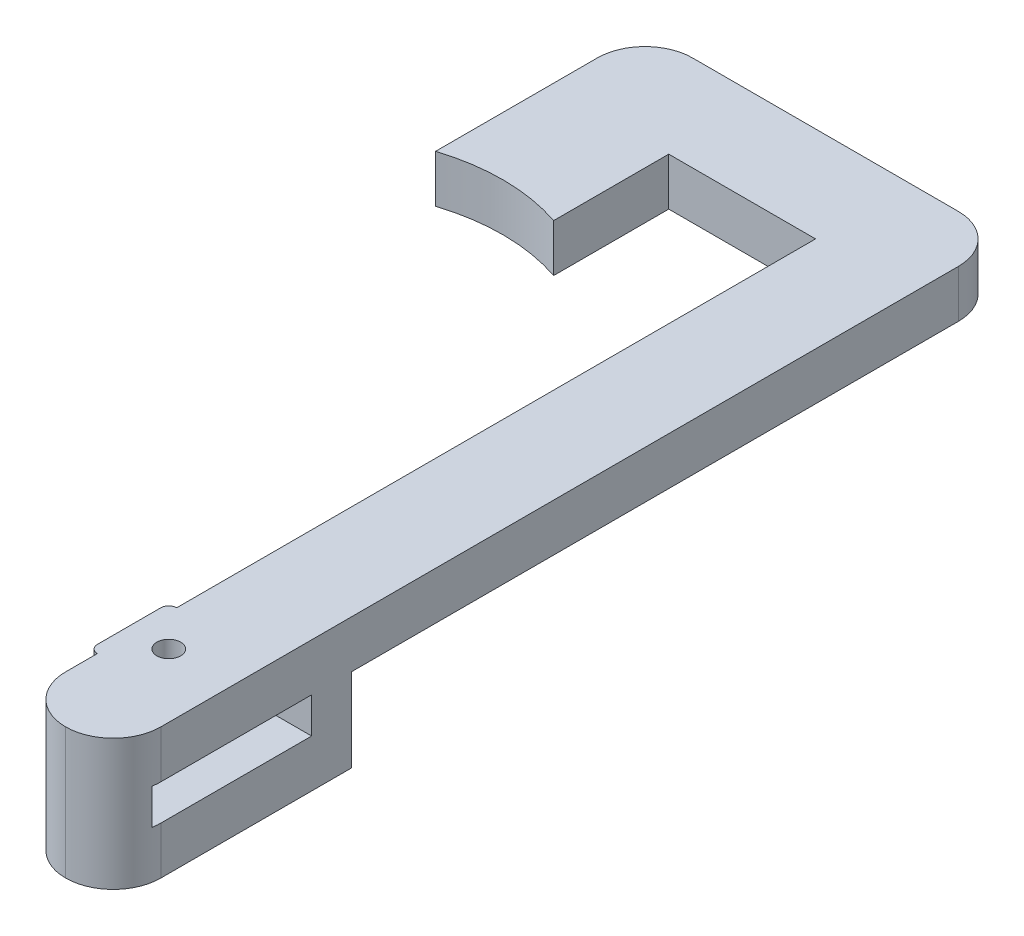
SolidWorks part; units mm, degrees
ref_plane "Front Plane" through (0, 0, 0) normal (0, 0, 1) x (1, 0, 0)
ref_plane "Top Plane" through (0, 0, 0) normal (0, 1, 0) x (1, 0, 0)
ref_plane "Right Plane" through (0, 0, 0) normal (1, 0, 0) x (0, 0, -1)
sketch "Sketch1" plane through (0, 0, 0) normal (0, 1, 0) x (1, 0, 0)
  line L0 (0, 0) -> (0, -7.5)
  line L15 (-2, -7.5) -> (4, -7.5)
  line L16 (-2, -7.5) -> (-2, 42.75)
  line L18 (4, -7.5) -> (4, 48.75)
  line L19 (-2, -2.9) -> (-2, -7.5)
  line L22 (0, 0) -> (-2, 0)
  line L23 (-11.25, 42.75) -> (-2, 42.75)
  line L26 (4, 48.75) -> (-18.75, 48.75)
  line L29 (-18.75, 48.75) -> (-18.75, 35.75)
  line L30 (-18.75, 35.75) -> (-11.25, 35.75)
  line L31 (-11.25, 42.75) -> (-11.25, 35.75)
  line L32 (0, 0) -> (4, 0)
  line L33 (-2, 42.75) -> (4, 42.75)
  line L34 (-18.75, 35.75) -> (-11.25, 35.75)
  line L35 (-18.75, 35.75) -> (-18.75, 28.3693)
  line L36 (-18.75, 28.3693) -> (-11.25, 28.3693)
  line L37 (-11.25, 35.75) -> (-11.25, 28.3693)
  line L38 (-2, 42.75) -> (-2, 48.75)
  line L39 (-11.25, 42.75) -> (-18.75, 42.75)
  line L40 (-11.25, 42.75) -> (-11.25, 48.75)
  line L42 (-2.5, 2.5) -> (-2, 2.5)
  line L43 (-2.5, 2.5) -> (-2.5, -2.5)
  line L44 (-2.5, -2.5) -> (-2, -2.5)
  line L45 (-2, 2.5) -> (-2, -2.5)
  line L46 (-2.5, 2.5) -> (-2, -2.5) construction
  line L47 (-2.5, -2.5) -> (-2, 2.5) construction
  point P0 (1, -7.5)
  point P4 (-2.25, 0)
  point P27 (0, 0)
  point P28 (0, 0)
  dimension "D1" = 9.25
  dimension "D2" = 2
  dimension "D3" = 4
  dimension "D4" = 7.5
extrude "Boss-Extrude1" add sketch "Sketch1" along normal blind 3
sketch "Sketch2" plane through (0, 3, 0) normal (0, 1, 0) x (1, 0, 0)
  circle A0 centre (-15.0919, 24.1296) radius 12
  point P2 (-15.0919, 24.1296)
extrude "Cut-Extrude1" cut sketch "Sketch2" against normal up to surface (3 mm away) up to face at (-5.4167, 0, -18.7282)
sketch "Sketch5" plane through (0, 0, 0) normal (0, -1, 0) x (1, 0, 0)
  line L0 (-2, 7.5) -> (-2, 2.5) construction
  line L1 (4, 7.5) -> (-2, 7.5)
  line L2 (4, 7.5) -> (4, 5)
  line L3 (4, 5) -> (-2, 5)
  line L4 (-2, 7.5) -> (-2, 5)
  line L5 (-2.5, 0) -> (4, 0)
  line L6 (-2.5, -2.5) -> (-2.5, 2.5) construction
  line L7 (4, 7.5) -> (4, -48.75) construction
  line L8 (-2, -7.5) -> (-2, -5)
  line L9 (4, -7.5) -> (-2, -7.5)
  line L10 (4, -7.5) -> (4, -5)
  line L11 (4, -5) -> (-2, -5)
  line M11 (4, -48.75) -> (4, 7.5)
  line M12 (4, 7.5) -> (-2, 7.5)
  line M13 (-2, 7.5) -> (-2, 2.5)
  line M17 (-2, -2.5) -> (-2, -42.75)
extrude "Boss-Extrude2" add sketch "Sketch5" along normal blind 5.25 contours L11 L9 M11 M17 | L3 M11 M12 M13
sketch "Sketch6" plane through (0, 0, 5) normal (0, 0, -1) x (-1, 0, 0)
  line L1 (-4, -5.25) -> (2, -5.25)
  line L2 (-4, -5.25) -> (-4, -2.25)
  line L3 (-4, -2.25) -> (2, -2.25)
  line L4 (2, -5.25) -> (2, -2.25)
  point P5 (0, 0)
  point P9 (0, 0)
extrude "Boss-Extrude3" add sketch "Sketch6" along normal up to surface (10 mm away) up to face at (1, -2.625, -5)
sketch "Sketch4" plane through (0, 3, 0) normal (0, 1, 0) x (1, 0, 0)
  circle A0 centre (0, 0) radius 0.75
extrude "Cut-Extrude2" cut sketch "Sketch4" against normal up to surface (8.25 mm away) up to face at (1, -5.25, 0)
fillet "Fillet1" radius 3 4 edges at (-18.75, 1.5, -48.75) (4, 1.5, -48.75) (4, -1.125, 7.5) (-2, -1.125, 7.5)
sketch "Sketch8" plane through (0, -2.25, 0) normal (0, 1, 0) x (1, 0, 0)
  line L1 (-2, 2.5) -> (-2.5, 2.5)
  line L2 (-2, 2.5) -> (-2, -2.5)
  line L3 (-2, -2.5) -> (-2.5, -2.5)
  line L4 (-2.5, 2.5) -> (-2.5, -2.5)
  point P4 (0, 0)
  point P5 (0, 0)
  point P6 (0, 0)
  point P7 (0, 0)
extrude "Boss-Extrude4" add sketch "Sketch8" against normal up to surface (3 mm away) up to face at (0, -5.25, -0.75)
fillet "Fillet2" radius 0.5 4 edges at (-2.5, 1.5, 2.5) (-2.5, 1.5, -2.5) (-2.5, -3.75, 2.5) (-2.5, -3.75, -2.5)
